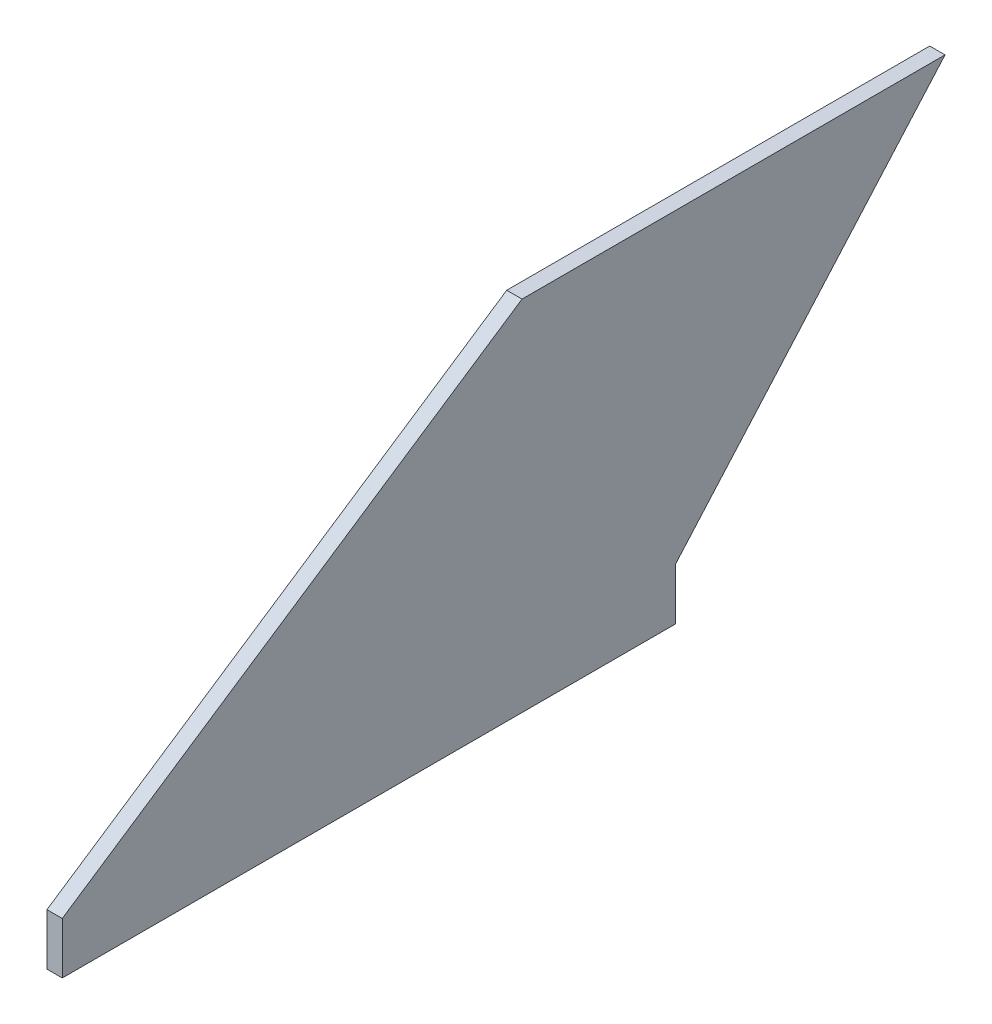
SolidWorks part; units mm, degrees
ref_plane "Front Plane" through (0, 0, 0) normal (0, 0, 1) x (1, 0, 0)
ref_plane "Top Plane" through (0, 0, 0) normal (0, 1, 0) x (1, 0, 0)
ref_plane "Right Plane" through (0, 0, 0) normal (1, 0, 0) x (0, 0, -1)
sketch "Sketch2" plane through (0, 0, 0) normal (1, 0, 0) x (0, 0, -1)
  line L0 (0, 0) -> (95.25, 63.5)
  line L1 (0, -10.6807) -> (127, -10.6807)
  line L2 (0, -10.6807) -> (0, 0)
  line L3 (0, 0) -> (127, 0) construction
  line L4 (127, -10.6807) -> (127, 0)
  line L5 (0, -10.6807) -> (127, 0) construction
  line L6 (0, 0) -> (127, -10.6807) construction
  line L7 (95.25, 63.5) -> (182.88, 63.5)
  line L8 (182.88, 63.5) -> (127, 0)
  point P0 (63.5, -5.3403)
  dimension "D1" = 95.25
  dimension "D2" = 63.5
  dimension "D3" = 182.88
  dimension "D4" = 127
  dimension "D5" = 10.6807
extrude "Boss-Extrude1" add sketch "Sketch2" along normal blind 3.175
equation "\"AIRFRAME_OD\"= 3.091in"
equation "\"AIRFRAME_ID\"= 3.00in"
equation "\"FLAT_T\" = 0.125in"
equation "\"COUPLER_OD\" = 2.998in"
equation "\"COUPLER_ID\" = 2.875in"
equation "\"NOSE_EXP_L\"= 3.5in"
equation "\"NOSE_SHOULDER_L\" = 5in"
equation "\"MAIN_L\" = 30in"
equation "\"RECO_COUP_L\" = 6in"
equation "\"RECO_SWITCH_L\" = 1.5in"
equation "\"RECO_ROD_X\" = 1.5in"
equation "\"DROGUE_L\" = 14in"
equation "\"ATS_FORE_COUP_L\" = 4in"
equation "\"ATS_AFT_COUP_L\" = 4in"
equation "\"ATS_ROD_X\" = 2in"
equation "\"LOWER_L\" = 16in"
equation "\"FIN_ROOT\" = 5in"
equation "\"FIN_X\" = 0.75in"
equation "\"FIN_N\" = 4"
equation "\"MOTOR_OD\" = 2.25in"
equation "\"MOTOR_ID\" = 2.126in"
equation "\"MOTOR_L\" = 8in"
equation "\"CR_AFT_X\" = 0.5in"
equation "\"CR_FORE_X\" = 6in"
equation "\"D1@Boss-Extrude1\"=\"FLAT_T\""
equation "\"D4@Sketch2\"=\"FIN_ROOT\""
equation "\"D5@Sketch2\"=(\"AIRFRAME_OD\"-\"MOTOR_OD\")*0.5"
